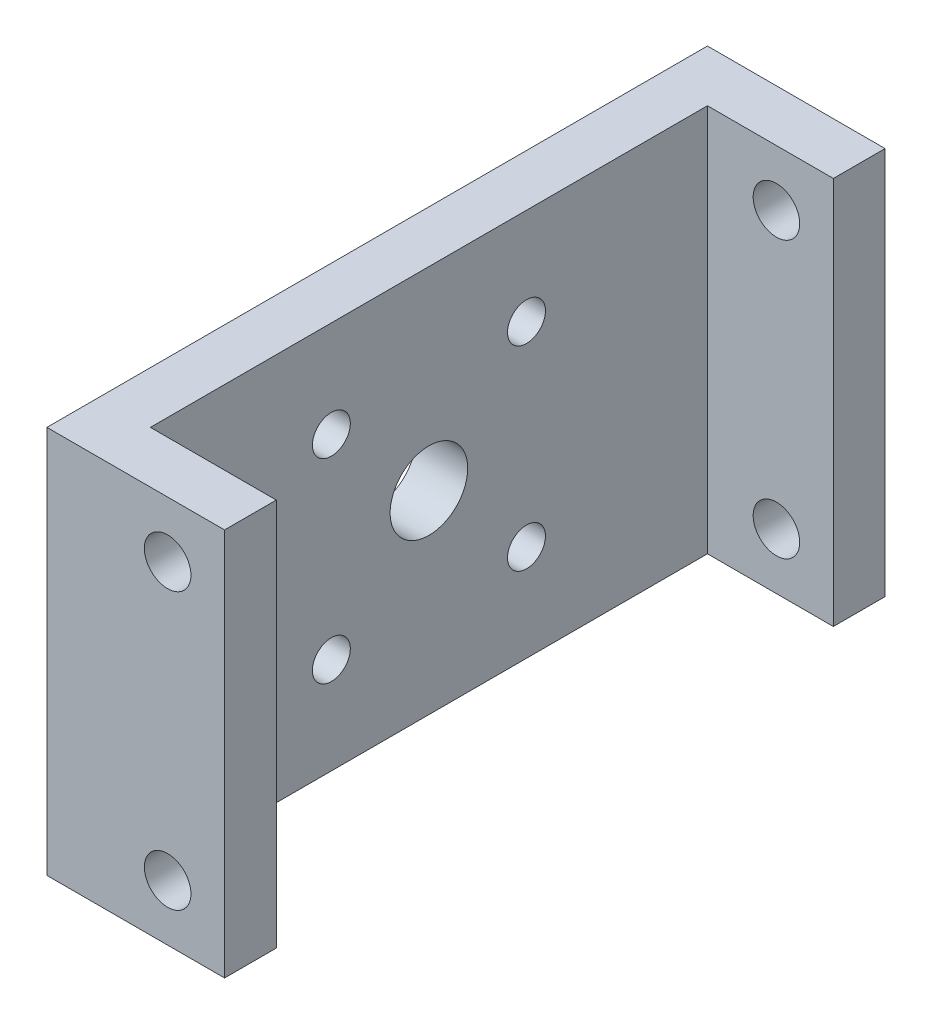
SolidWorks part; units mm, degrees
ref_plane "Front Plane" through (0, 0, 0) normal (0, 0, 1) x (1, 0, 0)
ref_plane "Top Plane" through (0, 0, 0) normal (0, 1, 0) x (1, 0, 0)
ref_plane "Right Plane" through (0, 0, 0) normal (1, 0, 0) x (0, 0, -1)
sketch "Sketch1" plane through (0, 0, 0) normal (1, 0, 0) x (0, 0, -1)
  line L0 (-14, 0) -> (-11, 0) construction
  line L1 (5.6569, 5.6569) -> (0, 0) construction
  line L2 (-16.15, 11.25) -> (-16.15, -11.25)
  line L3 (-19.15, 11.25) -> (19.15, 11.25)
  line L4 (-19.15, 11.25) -> (-19.15, -11.25)
  line L5 (-19.15, -11.25) -> (19.15, -11.25)
  line L6 (19.15, 11.25) -> (19.15, -11.25)
  line L7 (-19.15, 11.25) -> (19.15, -11.25) construction
  line L8 (-19.15, -11.25) -> (19.15, 11.25) construction
  line L10 (0, 5.005) -> (0, -5.005) construction
  line L11 (16.15, 11.25) -> (16.15, -11.25)
  line L12 (-2.25, 0) -> (14, 0) construction
  circle A1 centre (5.6569, 5.6569) radius 1.1
  circle A2 centre (0, 0) radius 2.25
  circle A3 centre (5.6569, -5.6569) radius 1.1
  circle A4 centre (-5.6569, -5.6569) radius 1.1
  circle A5 centre (-5.6569, 5.6569) radius 1.1
  dimension "D1" = 38.3
  dimension "D2" = 8
  dimension "D4" = 2.2
  dimension "D5" = 4.5
  dimension "D3" = 45
  dimension "D7" = 22.5
  dimension "D8" = 3
  dimension "D6" = 4
extrude "Boss-Extrude1" add sketch "Sketch1" along normal blind 3 contours L3 L5 A5 A4 A3 A2 A1 region at (0, 10.8564, 0)
extrude "Boss-Extrude5" add sketch "Sketch1<5>" along normal blind 10.3 contours L3 L11 L5 L6 | L4 L5 L2 L3 region at (0, 0, 17.65) region at (0, 0, -17.65)
sketch "Sketch1<5>" plane through (0, 0, 0) normal (1, 0, 0) x (0, 0, -1) same geometry as "Sketch1"
sketch "Sketch2" plane through (0, 0, 19.15) normal (0, 0, 1) x (1, 0, 0)
  line L0 (10.3, 11.25) -> (10.3, -11.25) construction
  circle A0 centre (7, 8) radius 1.35
  dimension "D2" = 2.7
  dimension "D1" = 8
  dimension "D3" = 3.3
extrude "Cut-Extrude1" cut sketch "Sketch2" against normal up to surface (38.3 mm away) up to face at (5.15, 0, -19.15)
mirror "Mirror1" about plane through (0, 0, 0) normal (0, 1, 0) of "Cut-Extrude1"
move or copy body "Body-Move/Copy1" [suppressed] bodies to move or copy 112
